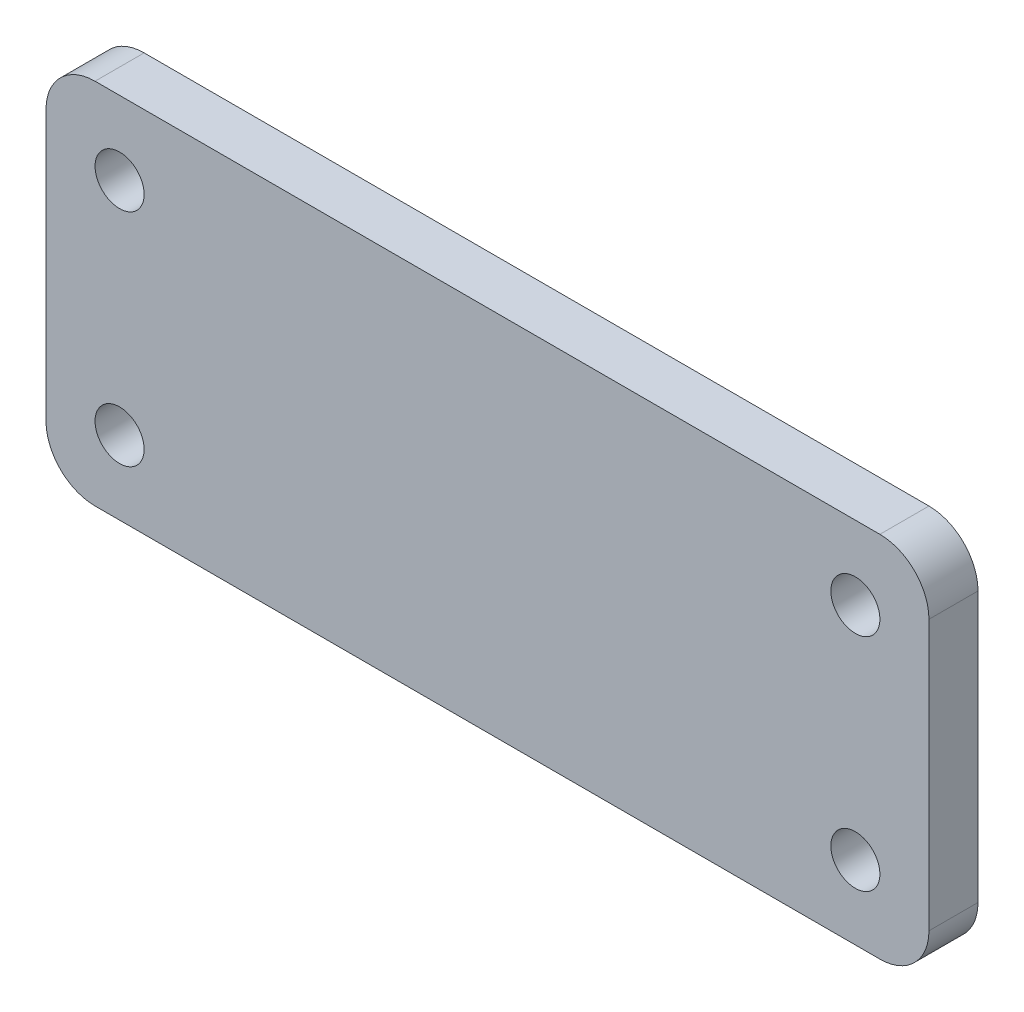
SolidWorks part; units mm, degrees
ref_plane "Front Plane" through (0, 0, 0) normal (0, 0, 1) x (1, 0, 0)
ref_plane "Top Plane" through (0, 0, 0) normal (0, 1, 0) x (1, 0, 0)
ref_plane "Right Plane" through (0, 0, 0) normal (1, 0, 0) x (0, 0, -1)
sketch "Sketch2" plane through (0, 0, 0) normal (0, 0, 1) x (1, 0, 0)
  line L1 (10, 0) -> (170, 0)
  line L2 (0, -10) -> (0, -65)
  line L3 (10, -75) -> (170, -75)
  line L4 (180, -10) -> (180, -65)
  arc A0 (170, 0) -> (180, -10) centre (170, -10) cw
  arc A1 (10, 0) -> (0, -10) centre (10, -10) ccw
  arc A2 (0, -65) -> (10, -75) centre (10, -65) ccw
  arc A3 (170, -75) -> (180, -65) centre (170, -65) ccw
  point P7 (0, 0)
  point P8 (21.2758, -14.0123)
  point P9 (180, 0)
  point P12 (0, 0)
  point P15 (0, -75)
  dimension "D3" = 10
  dimension "D4" = 10
  dimension "D5" = 10
  dimension "D6" = 10
  dimension "D1" = 180
  dimension "D2" = 75
extrude "Boss-Extrude1" add sketch "Sketch2" along normal blind 10 contours A3 L3 A2 L2 A1 L1 A0 L4
sketch "Sketch6" plane through (0, 0, 0) normal (0, 0, 1) x (1, 0, 0)
  line L0 (10, 0) -> (170, 0) construction
  line L1 (0, -10) -> (0, -65) construction
  line L2 (90, 29.3526) -> (90, -100.8166) construction
  line L3 (-14.8389, -37.5) -> (194.7176, -37.5) construction
  line L4 (10, -75) -> (170, -75) construction
  circle A0 centre (15, -15) radius 5
  circle A1 centre (165, -15) radius 5
  circle A2 centre (15, -60) radius 5
  circle A3 centre (165, -60) radius 5
  point P18 (0, 0)
  dimension "D1" = 10
  dimension "D2" = 15
  dimension "D3" = 15
  dimension "D4" = 90
  dimension "D5" = 37.5
extrude "Cut-Extrude1" cut sketch "Sketch6" along normal blind 10 contours A0
extrude "Cut-Extrude4" cut sketch "Sketch6<4>" along normal blind 10 contours A1 | A2 | A3
sketch "Sketch6<4>" plane through (0, 0, 0) normal (0, 0, 1) x (1, 0, 0) same geometry as "Sketch6"
